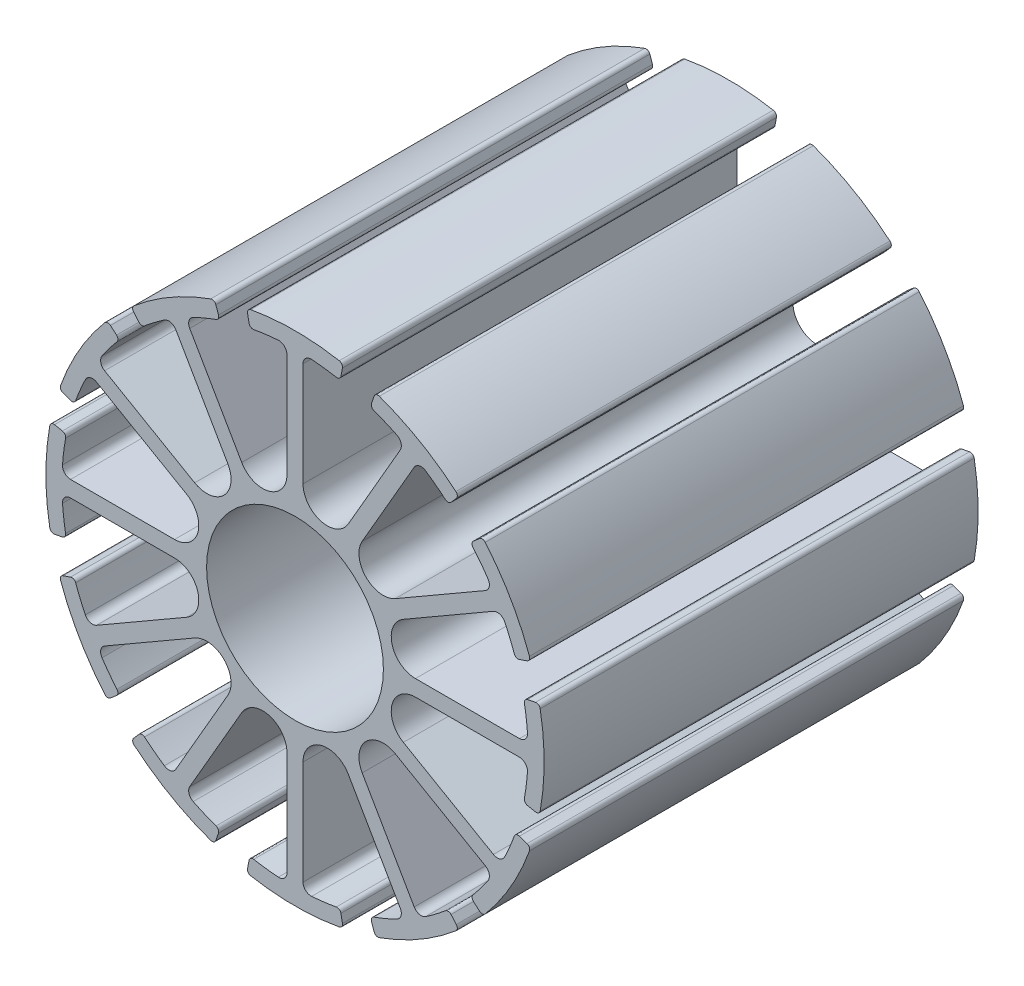
SolidWorks part; units mm, degrees
ref_plane "Plano frontal" through (0, 0, 0) normal (0, 0, 1) x (1, 0, 0)
ref_plane "Plano superior" through (0, 0, 0) normal (0, 1, 0) x (1, 0, 0)
ref_plane "Plano direito" through (0, 0, 0) normal (1, 0, 0) x (0, 0, -1)
sketch "Esboço1" plane through (0, 0, 0) normal (0, 0, 1) x (1, 0, 0)
  line L0 (0, 0) -> (0, 21.6977) construction
  line L1 (-3, 15.2069) -> (3, 15.2069) construction
  line L2 (-2.9523, 14.9603) -> (-2.8573, 14.4694)
  line L3 (-4.08, 13.9794) -> (-0.4462, 14.6828) construction
  line L4 (2.9523, 14.9603) -> (2.8572, 14.4694)
  line L5 (4.9234, 14.4322) -> (4.7602, 13.9595)
  line L6 (10.0369, 11.4799) -> (9.7091, 11.1023)
  line L7 (11.4799, 10.0369) -> (11.1022, 9.7092)
  line L8 (14.4321, 4.9234) -> (13.9595, 4.7603)
  line L9 (14.9603, 2.9523) -> (14.4694, 2.8572)
  line L10 (14.9603, -2.9523) -> (14.4694, -2.8572)
  line L11 (14.4321, -4.9234) -> (13.9595, -4.7603)
  line L12 (11.4799, -10.0369) -> (11.1022, -9.7091)
  line L13 (10.0369, -11.4799) -> (9.7091, -11.1023)
  line L14 (4.9234, -14.4322) -> (4.7602, -13.9595)
  line L15 (2.9523, -14.9603) -> (2.8572, -14.4694)
  line L16 (-2.9523, -14.9603) -> (-2.8573, -14.4694)
  line L17 (-4.9234, -14.4322) -> (-4.7603, -13.9595)
  line L18 (-10.0369, -11.4799) -> (-9.7092, -11.1023)
  line L19 (-11.4799, -10.0369) -> (-11.1023, -9.7091)
  line L20 (-14.4322, -4.9234) -> (-13.9595, -4.7603)
  line L21 (-14.9604, -2.9523) -> (-14.4694, -2.8572)
  line L22 (-14.9604, 2.9523) -> (-14.4694, 2.8572)
  line L23 (-14.4322, 4.9234) -> (-13.9595, 4.7603)
  line L24 (-11.4799, 10.0369) -> (-11.1023, 9.7092)
  line L25 (-10.0369, 11.4799) -> (-9.7092, 11.1023)
  line L26 (-4.9234, 14.4322) -> (-4.7603, 13.9595)
  line L27 (-0.5, 13.9642) -> (-0.5, 7.4935)
  line L28 (0.5, 13.9642) -> (0.5, 7.4935)
  line L29 (6.5491, 12.3434) -> (3.3137, 6.7396)
  line L30 (7.4151, 11.8434) -> (4.1798, 6.2396)
  line L31 (11.8434, 7.4151) -> (6.2396, 4.1798)
  line L32 (12.3434, 6.5491) -> (6.7396, 3.3138)
  line L33 (13.9642, 0.5) -> (7.4935, 0.5)
  line L34 (13.9642, -0.5) -> (7.4935, -0.5)
  line L35 (12.3434, -6.5491) -> (6.7396, -3.3137)
  line L36 (11.8434, -7.4151) -> (6.2396, -4.1798)
  line L37 (7.4151, -11.8434) -> (4.1798, -6.2396)
  line L38 (6.5491, -12.3434) -> (3.3138, -6.7396)
  line L39 (0.5, -13.9642) -> (0.5, -7.4935)
  line L40 (-0.5, -13.9642) -> (-0.5, -7.4935)
  line L41 (-6.5491, -12.3434) -> (-3.3137, -6.7396)
  line L42 (-7.4151, -11.8434) -> (-4.1798, -6.2396)
  line L43 (-11.8434, -7.4152) -> (-6.2396, -4.1798)
  line L44 (-12.3434, -6.5491) -> (-6.7396, -3.3138)
  line L45 (-13.9643, -0.5) -> (-7.4935, -0.5)
  line L46 (-13.9643, 0.5) -> (-7.4935, 0.5)
  line L47 (-12.3434, 6.5491) -> (-6.7396, 3.3137)
  line L48 (-11.8434, 7.4151) -> (-6.2396, 4.1798)
  line L49 (-7.4152, 11.8434) -> (-4.1798, 6.2396)
  line L50 (-6.5491, 12.3434) -> (-3.3138, 6.7396)
  arc A0 (-5.2444, 14.5859) -> (-10.0096, 11.8347) centre (0, 0) ccw
  arc A1 (-4.9119, 13.6427) -> (-6.3346, 13.0432) centre (0, 0) ccw
  circle A2 centre (0, 0) radius 6.25 construction
  circle A3 centre (0, 0) radius 5.5
  arc A4 (2.5675, 14.2709) -> (1.0357, 14.463) centre (0, 0) ccw
  arc A5 (2.7512, 15.2539) -> (-2.7512, 15.2539) centre (0, 0) ccw
  arc A6 (9.359, 11.0752) -> (8.1284, 12.0074) centre (0, 0) ccw
  arc A7 (10.0095, 11.8347) -> (5.2443, 14.5859) centre (0, 0) ccw
  arc A8 (-11.8347, 10.0096) -> (-14.5859, 5.2443) centre (0, 0) ccw
  arc A9 (-11.0752, 9.359) -> (-12.0075, 8.1284) centre (0, 0) ccw
  arc A10 (-15.2539, 2.7512) -> (-15.2539, -2.7512) centre (0, 0) ccw
  arc A11 (-14.2709, 2.5675) -> (-14.463, 1.0357) centre (0, 0) ccw
  arc A12 (-14.5859, -5.2443) -> (-11.8347, -10.0095) centre (0, 0) ccw
  arc A13 (-13.6427, -4.9119) -> (-13.0432, -6.3346) centre (0, 0) ccw
  arc A14 (-10.0096, -11.8346) -> (-5.2444, -14.5858) centre (0, 0) ccw
  arc A15 (-9.359, -11.0752) -> (-8.1284, -12.0075) centre (0, 0) ccw
  arc A16 (-2.7512, -15.2539) -> (2.7512, -15.2539) centre (0, 0) ccw
  arc A17 (-2.5676, -14.2709) -> (-1.0357, -14.463) centre (0, 0) ccw
  arc A18 (4.9119, -13.6427) -> (6.3345, -13.0431) centre (0, 0) ccw
  arc A19 (5.2443, -14.5858) -> (10.0095, -11.8346) centre (0, 0) ccw
  arc A20 (11.0752, -9.359) -> (12.0074, -8.1284) centre (0, 0) ccw
  arc A21 (11.8346, -10.0095) -> (14.5858, -5.2443) centre (0, 0) ccw
  arc A22 (14.2709, -2.5675) -> (14.4629, -1.0357) centre (0, 0) ccw
  arc A23 (15.2539, -2.7512) -> (15.2539, 2.7512) centre (0, 0) ccw
  arc A24 (13.6427, 4.9119) -> (13.0431, 6.3345) centre (0, 0) ccw
  arc A25 (14.5858, 5.2443) -> (11.8346, 10.0096) centre (0, 0) ccw
  arc A26 (0.5, 7.4935) -> (3.3137, 6.7396) centre (2.0079, 7.4935) ccw
  arc A27 (4.1798, 6.2396) -> (6.2396, 4.1798) centre (5.4856, 5.4857) ccw
  arc A28 (6.7396, 3.3138) -> (7.4935, 0.5) centre (7.4935, 2.0079) ccw
  arc A29 (7.4935, -0.5) -> (6.7396, -3.3137) centre (7.4935, -2.0079) ccw
  arc A30 (6.2396, -4.1798) -> (4.1798, -6.2396) centre (5.4857, -5.4856) ccw
  arc A31 (3.3138, -6.7396) -> (0.5, -7.4935) centre (2.0079, -7.4935) ccw
  arc A32 (-0.5, -7.4935) -> (-3.3137, -6.7396) centre (-2.0079, -7.4935) ccw
  arc A33 (-4.1798, -6.2396) -> (-6.2396, -4.1798) centre (-5.4856, -5.4857) ccw
  arc A34 (-6.7396, -3.3138) -> (-7.4935, -0.5) centre (-7.4935, -2.0079) ccw
  arc A35 (-7.4935, 0.5) -> (-6.7396, 3.3137) centre (-7.4935, 2.0079) ccw
  arc A36 (-6.2396, 4.1798) -> (-4.1798, 6.2396) centre (-5.4857, 5.4856) ccw
  arc A37 (-3.3138, 6.7396) -> (-0.5, 7.4935) centre (-2.0079, 7.4935) ccw
  arc A38 (-8.1285, 12.0074) -> (-9.359, 11.0752) centre (0, 0) ccw
  arc A39 (-1.0357, 14.463) -> (-2.5676, 14.2709) centre (0, 0) ccw
  arc A40 (6.3345, 13.0432) -> (4.9119, 13.6427) centre (0, 0) ccw
  arc A41 (12.0074, 8.1284) -> (11.0752, 9.359) centre (0, 0) ccw
  arc A42 (13.0431, -6.3345) -> (13.6427, -4.9119) centre (0, 0) ccw
  arc A43 (14.4629, 1.0357) -> (14.2709, 2.5675) centre (0, 0) ccw
  arc A44 (8.1284, -12.0074) -> (9.359, -11.0752) centre (0, 0) ccw
  arc A45 (1.0357, -14.463) -> (2.5675, -14.2709) centre (0, 0) ccw
  arc A46 (-6.3345, -13.0432) -> (-4.9119, -13.6427) centre (0, 0) ccw
  arc A47 (-13.0432, 6.3345) -> (-13.6427, 4.9119) centre (0, 0) ccw
  arc A48 (-14.463, -1.0357) -> (-14.2709, -2.5675) centre (0, 0) ccw
  arc A49 (-12.0074, -8.1285) -> (-11.0752, -9.359) centre (0, 0) ccw
  arc A50 (-6.3346, 13.0432) -> (-6.5491, 12.3434) centre (-6.1161, 12.5934) ccw
  arc A51 (-7.4152, 11.8434) -> (-8.1285, 12.0074) centre (-7.8482, 11.5934) ccw
  arc A52 (-4.9234, 14.4322) -> (-5.2444, 14.5859) centre (-5.1598, 14.3506) ccw
  arc A53 (-4.7603, 13.9595) -> (-4.9119, 13.6427) centre (-4.9966, 13.8779) cw
  arc A54 (-9.7092, 11.1023) -> (-9.359, 11.0752) centre (-9.5204, 11.2661) ccw
  arc A55 (-10.0096, 11.8347) -> (-10.0369, 11.4799) centre (-9.8481, 11.6438) ccw
  arc A56 (2.9523, 14.9603) -> (2.7512, 15.2539) centre (2.7068, 15.0079) ccw
  arc A57 (2.5675, 14.2709) -> (2.8572, 14.4694) centre (2.6118, 14.5169) ccw
  arc A58 (-2.9523, 14.9603) -> (-2.7512, 15.2539) centre (-2.7068, 15.0079) cw
  arc A59 (-2.5676, 14.2709) -> (-2.8573, 14.4694) centre (-2.6118, 14.5169) cw
  arc A60 (1.0357, 14.463) -> (0.5, 13.9642) centre (1, 13.9642) ccw
  arc A61 (-0.5, 13.9642) -> (-1.0357, 14.463) centre (-1, 13.9642) ccw
  arc A62 (13.0431, 6.3345) -> (12.3434, 6.5491) centre (12.5934, 6.1161) ccw
  arc A63 (11.8434, 7.4151) -> (12.0074, 8.1284) centre (11.5934, 7.8482) ccw
  arc A64 (7.4151, 11.8434) -> (8.1284, 12.0074) centre (7.8481, 11.5934) cw
  arc A65 (6.3345, 13.0432) -> (6.5491, 12.3434) centre (6.1161, 12.5934) cw
  arc A66 (14.4629, -1.0357) -> (13.9642, -0.5) centre (13.9642, -1) ccw
  arc A67 (14.4629, 1.0357) -> (13.9642, 0.5) centre (13.9642, 1) cw
  arc A68 (1.0357, -14.463) -> (0.5, -13.9642) centre (1, -13.9642) cw
  arc A69 (6.5491, -12.3434) -> (6.3345, -13.0431) centre (6.1161, -12.5934) cw
  arc A70 (8.1284, -12.0074) -> (7.4151, -11.8434) centre (7.8482, -11.5934) cw
  arc A71 (12.0074, -8.1284) -> (11.8434, -7.4151) centre (11.5934, -7.8481) ccw
  arc A72 (12.3434, -6.5491) -> (13.0431, -6.3345) centre (12.5934, -6.1161) ccw
  arc A73 (-1.0357, -14.463) -> (-0.5, -13.9642) centre (-1, -13.9642) ccw
  arc A74 (-12.0074, -8.1285) -> (-11.8434, -7.4152) centre (-11.5934, -7.8482) cw
  arc A75 (-12.3434, -6.5491) -> (-13.0432, -6.3346) centre (-12.5934, -6.1161) cw
  arc A76 (-7.4151, -11.8434) -> (-8.1284, -12.0075) centre (-7.8481, -11.5934) cw
  arc A77 (-6.5491, -12.3434) -> (-6.3345, -13.0432) centre (-6.1161, -12.5934) ccw
  arc A78 (-14.463, 1.0357) -> (-13.9643, 0.5) centre (-13.9643, 1) ccw
  arc A79 (-13.9643, -0.5) -> (-14.463, -1.0357) centre (-13.9643, -1) ccw
  arc A80 (-12.0075, 8.1284) -> (-11.8434, 7.4151) centre (-11.5934, 7.8481) ccw
  arc A81 (-12.3434, 6.5491) -> (-13.0432, 6.3345) centre (-12.5934, 6.1161) ccw
  arc A82 (13.6427, 4.9119) -> (13.9595, 4.7603) centre (13.8779, 4.9966) ccw
  arc A83 (14.4321, 4.9234) -> (14.5858, 5.2443) centre (14.3506, 5.1597) ccw
  arc A84 (11.8346, 10.0096) -> (11.4799, 10.0369) centre (11.6437, 9.8481) ccw
  arc A85 (11.1022, 9.7092) -> (11.0752, 9.359) centre (11.2661, 9.5203) ccw
  arc A86 (9.7091, 11.1023) -> (9.359, 11.0752) centre (9.5203, 11.2661) cw
  arc A87 (10.0369, 11.4799) -> (10.0095, 11.8347) centre (9.8481, 11.6438) ccw
  arc A88 (4.9234, 14.4322) -> (5.2443, 14.5859) centre (5.1597, 14.3506) cw
  arc A89 (4.7602, 13.9595) -> (4.9119, 13.6427) centre (4.9966, 13.8779) ccw
  arc A90 (15.2539, -2.7512) -> (14.9603, -2.9523) centre (15.0078, -2.7068) cw
  arc A91 (14.2709, -2.5675) -> (14.4694, -2.8572) centre (14.5169, -2.6118) ccw
  arc A92 (14.9603, 2.9523) -> (15.2539, 2.7512) centre (15.0078, 2.7068) cw
  arc A93 (14.4694, 2.8572) -> (14.2709, 2.5675) centre (14.5169, 2.6118) ccw
  arc A94 (11.4799, -10.0369) -> (11.8346, -10.0095) centre (11.6437, -9.8481) ccw
  arc A95 (11.1022, -9.7091) -> (11.0752, -9.359) centre (11.2661, -9.5203) cw
  arc A96 (13.6427, -4.9119) -> (13.9595, -4.7603) centre (13.8779, -4.9966) cw
  arc A97 (14.4321, -4.9234) -> (14.5858, -5.2443) centre (14.3506, -5.1597) cw
  arc A98 (9.359, -11.0752) -> (9.7091, -11.1023) centre (9.5203, -11.2661) cw
  arc A99 (10.0369, -11.4799) -> (10.0095, -11.8346) centre (9.8481, -11.6438) cw
  arc A100 (5.2443, -14.5858) -> (4.9234, -14.4322) centre (5.1597, -14.3506) cw
  arc A101 (4.7602, -13.9595) -> (4.9119, -13.6427) centre (4.9966, -13.8779) cw
  arc A102 (-2.5676, -14.2709) -> (-2.8573, -14.4694) centre (-2.6118, -14.5169) ccw
  arc A103 (-2.9523, -14.9603) -> (-2.7512, -15.2539) centre (-2.7068, -15.0078) ccw
  arc A104 (2.5675, -14.2709) -> (2.8572, -14.4694) centre (2.6118, -14.5169) cw
  arc A105 (2.9523, -14.9603) -> (2.7512, -15.2539) centre (2.7068, -15.0078) cw
  arc A106 (-9.359, -11.0752) -> (-9.7092, -11.1023) centre (-9.5204, -11.2661) ccw
  arc A107 (-10.0369, -11.4799) -> (-10.0096, -11.8346) centre (-9.8481, -11.6438) ccw
  arc A108 (-4.9119, -13.6427) -> (-4.7603, -13.9595) centre (-4.9966, -13.8779) cw
  arc A109 (-4.9234, -14.4322) -> (-5.2444, -14.5858) centre (-5.1598, -14.3506) cw
  arc A110 (-13.6427, -4.9119) -> (-13.9595, -4.7603) centre (-13.8779, -4.9966) ccw
  arc A111 (-14.4322, -4.9234) -> (-14.5859, -5.2443) centre (-14.3506, -5.1597) ccw
  arc A112 (-11.1023, -9.7091) -> (-11.0752, -9.359) centre (-11.2661, -9.5203) ccw
  arc A113 (-11.8347, -10.0095) -> (-11.4799, -10.0369) centre (-11.6438, -9.8481) ccw
  arc A114 (-14.9604, 2.9523) -> (-15.2539, 2.7512) centre (-15.0079, 2.7068) ccw
  arc A115 (-14.4694, 2.8572) -> (-14.2709, 2.5675) centre (-14.5169, 2.6118) cw
  arc A116 (-15.2539, -2.7512) -> (-14.9604, -2.9523) centre (-15.0079, -2.7068) ccw
  arc A117 (-14.4694, -2.8572) -> (-14.2709, -2.5675) centre (-14.5169, -2.6118) ccw
  arc A118 (-11.0752, 9.359) -> (-11.1023, 9.7092) centre (-11.2661, 9.5203) ccw
  arc A119 (-11.4799, 10.0369) -> (-11.8347, 10.0096) centre (-11.6438, 9.8481) ccw
  arc A120 (-14.5859, 5.2443) -> (-14.4322, 4.9234) centre (-14.3506, 5.1597) ccw
  arc A121 (-13.6427, 4.9119) -> (-13.9595, 4.7603) centre (-13.8779, 4.9966) cw
  point P59 (0, 0)
  point P60 (1.6136, 6.0381)
  point P107 (0, 0)
  point P140 (2.8099, 14.2251)
  point P144 (0, 0)
  point P150 (-2.81, 14.2251)
  point P155 (-0.5, 14.4914)
  point P174 (-12.2999, -7.6787)
  point P185 (-14.4914, -0.5)
  point P190 (-12.7999, 6.8127)
  dimension "D1" = 90
  dimension "D2" = 31
  dimension "D3" = 29
  dimension "D4" = 3
  dimension "D5" = 12.5
  dimension "D6" = 11
  dimension "D9" = 0.5
  dimension "D11" = 0.25
  dimension "D12" = 0.25
  dimension "D13" = 0.5
  dimension "D15" = 0.5
  dimension "D16" = 0.5
  dimension "D17" = 0.5
  dimension "D18" = 0.5
  dimension "D19" = 0.5
  dimension "D20" = 0.5
  dimension "D21" = 0.5
  dimension "D22" = 0.25
  dimension "D23" = 0.25
  dimension "D24" = 0.25
  dimension "D25" = 0.25
  dimension "D26" = 0.25
  dimension "D27" = 0.25
  dimension "D28" = 0.25
  dimension "D29" = 0.25
  dimension "D30" = 0.25
  dimension "D7" = 0.5
  dimension "D8" = 0.5
  dimension "D10" = 12
  dimension "D14" = 12
extrude "Ressalto-extrusão1" add sketch "Esboço1" along normal mid plane 27 contours A3 | L46 A35 L47 A81 A47 A121 L23 A120 A8 A119 L24 A118 A9 A80 L48 A36 L49 A51 A38 A54 L25 A55 A0 A52 L26 A53 A1 A50 L50 A37 L27 A61 A39 A59 L2 A58 A5 A56 L4 A57 A4 A60 L28 A26 L29 A65 A40 A89 L5 A88 A7 A87 L6 A86 A6 A64 L30 A27 L31 A63 A41 A85 L7 A84 A25 A83 L8 A82 A24 A62 L32 A28 L33 A67 A43 A93 L9 A92 A23 A90 L10 A91 A22 A66 L34 A29 L35 A72 A42 A96 L11 A97 A21 A94 L12 A95 A20 A71 L36 A30 L37 A70 A44 A98 L13 A99 A19 A100 L14 A101 A18 A69 L38 A31 L39 A68 A45 A104 L15 A105 A16 A103 L16 A102 A17 A73 L40 A32 L41 A77 A46 A108 L17 A109 A14 A107 L18 A106 A15 A76 L42 A33 L43 A74 A49 A112 L19 A113 A12 A111 L20 A110 A13 A75 L44 A34 L45 A79 A48 A117 L21 A116 A10 A114 L22 A115 A11 A78 region at (0, 0, 0)
ref_axis "Eixo1" through (0, 0, 13.5) along (0, 0, -1)
